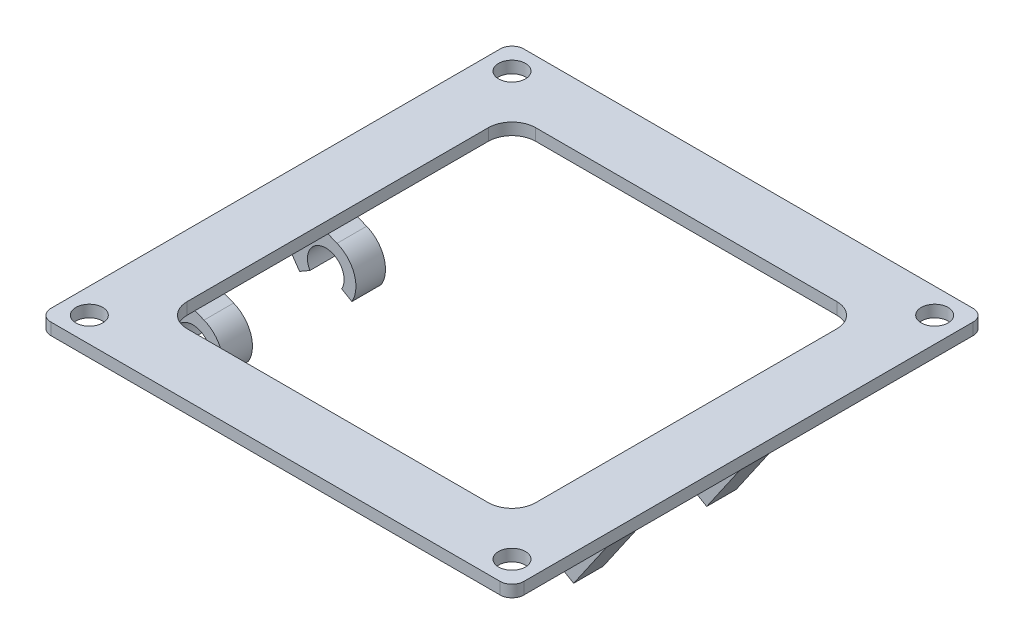
SolidWorks part; units mm, degrees
ref_plane "Front Plane" through (0, 0, 0) normal (0, 0, 1) x (1, 0, 0)
ref_plane "Top Plane" through (0, 0, 0) normal (0, 1, 0) x (1, 0, 0)
ref_plane "Right Plane" through (0, 0, 0) normal (1, 0, 0) x (0, 0, -1)
ref_plane "Plane5" through (0, 1.4, 0) normal (0, 1, 0) x (1, 0, 0)
sketch "Sketch1" plane through (0, 1.4, 0) normal (0, 1, 0) x (1, 0, 0)
  line L0 (-30, 40.97) -> (30, 40.97) construction
  line L1 (40, -16.53) -> (-40, -16.53)
  line L2 (40, -16.53) -> (40, 40.97)
  line L3 (40, 40.97) -> (-40, 40.97)
  line L4 (-40, -16.53) -> (-40, 40.97)
  line L5 (40, -16.53) -> (-40, 40.97) construction
  line L6 (40, 40.97) -> (-40, -16.53) construction
  line L8 (45.85, -16.53) -> (-45.85, -16.53) construction
  line L9 (0, 0) -> (0, 83.8599) construction
  point P0 (-15.6329, 0.9838)
  point P13 (0, 12.22)
  dimension "D1" = 80
extrude "Boss-Extrude1" add sketch "Sketch1" along normal blind 8
sketch "Sketch3" plane through (0, 0, -36.97) normal (0, 0, -1) x (-1, 0, 0)
  line L0 (-40, 1.4) -> (-34.1957, -6.9994)
  line L1 (-28.0906, 0.6291) -> (-30, 1.4)
  line L2 (0, 0) -> (0, -23.3047) construction
  line L3 (-40, 1.4) -> (-30, 1.4)
  line L11 (40, 1.4) -> (-40, 1.4) construction
  line L12 (-40, 9.4) -> (-40, 1.4) construction
  line L13 (40, 1.4) -> (30, 1.4)
  line L14 (28.0906, 0.6291) -> (30, 1.4)
  line L15 (40, 1.4) -> (34.1957, -6.9994)
  arc A0 (-34.1957, -6.9994) -> (-28.0906, 0.6291) centre (-30, -4.1) ccw
  circle A2 centre (-30, -4.1) radius 3.1
  arc A7 (34.1957, -6.9994) -> (28.0906, 0.6291) centre (30, -4.1) cw
  circle A8 centre (30, -4.1) radius 3.1
  point P2 (0, 0)
  point P5 (-35, 1.4)
  point P9 (-35.1, 1.4)
  point P14 (-35.1, 1.4)
  point P21 (-40, 1.4)
  point P23 (-35.1, -3.0527)
  point P24 (0, 0)
  point P25 (-40, 1.4)
  dimension "D1" = 2
  dimension "D2" = 6.2
  dimension "D3" = 10
extrude "Boss-Extrude2" add sketch "Sketch3" against normal blind 5 from offset 10 contours A0 L0 L3 L1 A2 | L15 A7 L14 L13 region at (35, 1.2155, -36.97) region at (-36.9461, -2.6948, -36.97) offset against normal yes
ref_plane "Plane1" through (0, 0, -13.22) normal (0, 0, 1) x (1, 0, 0)
mirror "Mirror1" about plane through (0, 0, -13.22) normal (0, 0, 1) of "Boss-Extrude2"
sketch "Sketch4" plane through (0, 0, -21.97) normal (0, 0, -1) x (-1, 0, 0)
  line L0 (-30, -4.1) -> (-20, -9.8735)
  line L1 (-20, -9.8735) -> (-40, -9.8735)
  line L2 (-40, -9.8735) -> (-30, -4.1)
  line L3 (0, 0) -> (0, -31.947) construction
  line L4 (20, -9.8735) -> (40, -9.8735)
  line L5 (30, -4.1) -> (20, -9.8735)
  line L6 (40, -9.8735) -> (30, -4.1)
  dimension "D1" = 20
  dimension "D2" = 120
extrude "Cut-Extrude1" cut sketch "Sketch4" against normal blind 63 and the other way blind 10
other "Move Face1" flip direction yes face at (0, 9.4, -12.22) offset 6 parameters "D1"=6
sketch "Sketch5" plane through (0, 3.4, 0) normal (0, 1, 0) x (1, 0, 0)
  line L5 (-40, 63.4699) -> (40, 63.4699)
  line L6 (-40, 63.4699) -> (-40, -16.53)
  line L8 (-40, -16.53) -> (40, -16.53)
  line L11 (40, 63.4699) -> (40, -16.53)
  line L14 (38, 63.4699) -> (20.6155, 63.4699) construction
extrude "Boss-Extrude3" add sketch "Sketch5" against normal blind 2
fillet "Fillet1" radius 2 4 edges at (-40, 2.4, 16.53) (40, 2.4, 16.53) (-40, 2.4, -63.4699) (40, 2.4, -63.4699)
sketch "Sketch6" plane through (0, 3.4, 0) normal (0, 1, 0) x (1, 0, 0)
  line L0 (35.75, 59.2199) -> (39.4142, 62.8841) construction
  line L1 (35.75, 59.2199) -> (-35.75, 59.2199) construction
  line L2 (35.75, 59.2199) -> (35.75, -12.28) construction
  line L3 (35.75, -12.28) -> (-35.75, -12.28) construction
  line L4 (-35.75, 59.2199) -> (-35.75, -12.28) construction
  line L5 (-35.75, -12.28) -> (-39.4142, -15.9442) construction
  circle A0 centre (35.75, 59.2199) radius 2.275
  circle A1 centre (35.75, -12.28) radius 2.275
  circle A2 centre (-35.75, 59.2199) radius 2.275
  circle A3 centre (-35.75, -12.28) radius 2.275
  circle A4 centre (35.75, 59.2199) radius 2 construction
  circle A5 centre (35.75, 59.2199) radius 2 construction
  arc A6 (40, 61.4699) -> (38, 63.4699) centre (38, 61.4699) ccw construction
  arc A7 (-40, -14.53) -> (-38, -16.53) centre (-38, -14.53) ccw construction
  point P8 (0, 0)
  point P11 (39.4142, 62.6791)
  point P14 (-39.4142, -15.9442)
  point P18 (39.4142, 62.6791)
  point P20 (-35.5449, 59.0149)
  point P22 (-35.7428, 59.11)
  point P23 (0, 0)
  dimension "D2" = 4.55
extrude "Cut-Extrude2" cut sketch "Sketch6" against normal blind 2
sketch "Sketch7" plane through (0, 3.4, 0) normal (0, 1, 0) x (1, 0, 0)
  line L0 (35.75, 59.2199) -> (-35.75, -12.28) construction
  line L2 (-29.468, -5.9981) -> (29.4681, -5.9981)
  line L3 (-29.468, -5.9981) -> (-29.468, 52.938)
  line L4 (-29.468, 52.938) -> (29.4681, 52.938)
  line L5 (29.4681, -5.9981) -> (29.4681, 52.938)
  line L6 (-29.468, -5.9981) -> (29.4681, 52.938) construction
  line L7 (-29.468, 52.938) -> (29.4681, -5.9981) construction
  point P4 (0, 23.4699)
  dimension "D1" = 8.884
extrude "Cut-Extrude3" cut sketch "Sketch7" against normal blind 2
fillet "Fillet2" radius 4 4 edges at (29.4681, 2.4, -52.938) (29.4681, 2.4, 5.9981) (-29.468, 2.4, 5.9981) (-29.468, 2.4, -52.938)
